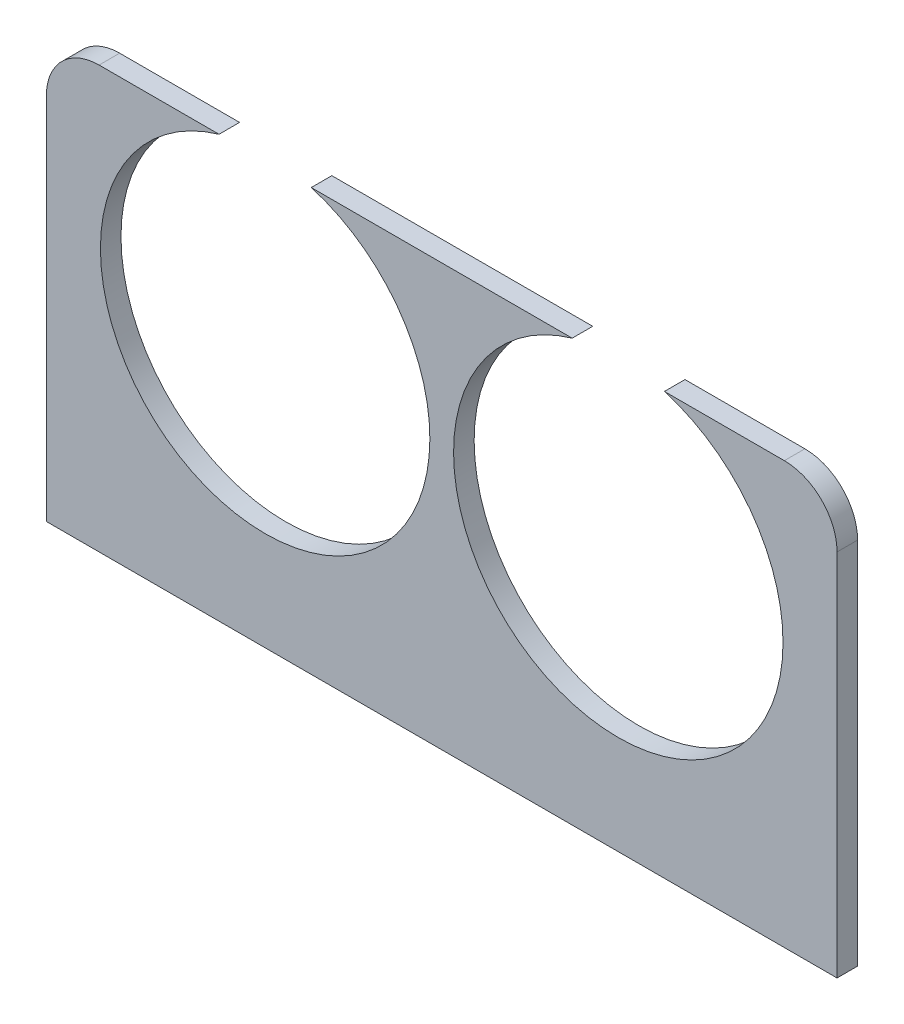
SolidWorks part; units mm, degrees
ref_plane "Front Plane" through (0, 0, 0) normal (0, 0, 1) x (1, 0, 0)
ref_plane "Top Plane" through (0, 0, 0) normal (0, 1, 0) x (1, 0, 0)
ref_plane "Right Plane" through (0, 0, 0) normal (1, 0, 0) x (0, 0, -1)
sketch "Sketch1" plane through (0, 0, 0) normal (0, 0, 1) x (1, 0, 0)
  line L0 (-6.7, 2) -> (6.7, 2) construction
  line L1 (-15, -8) -> (15, -8)
  line L2 (-15, -8) -> (-15, 8)
  line L3 (-15, 8) -> (15, 8)
  line L4 (15, -8) -> (15, 8)
  line L5 (-15, -8) -> (15, 8) construction
  line L6 (-15, 8) -> (15, -8) construction
  line L7 (-15, 2) -> (15, 2) construction
  circle A0 centre (-6.7, 2) radius 6.25
  circle A1 centre (6.7, 2) radius 6.25
  point P4 (0, 0)
  point P6 (0, 2)
  dimension "D1" = 12.5
  dimension "D2" = 13.4
  dimension "D3" = 6
  dimension "D4" = 30
  dimension "D5" = 16
extrude "Boss-Extrude1" add sketch "Sketch1" along normal blind 0.78 contours L3 A1 A0 L2 L1 L4 region at (0, -2.0421, 0)
fillet "Fillet1" radius 2 2 edges at (15, 8, 0.39) (-15, 8, 0.39)
